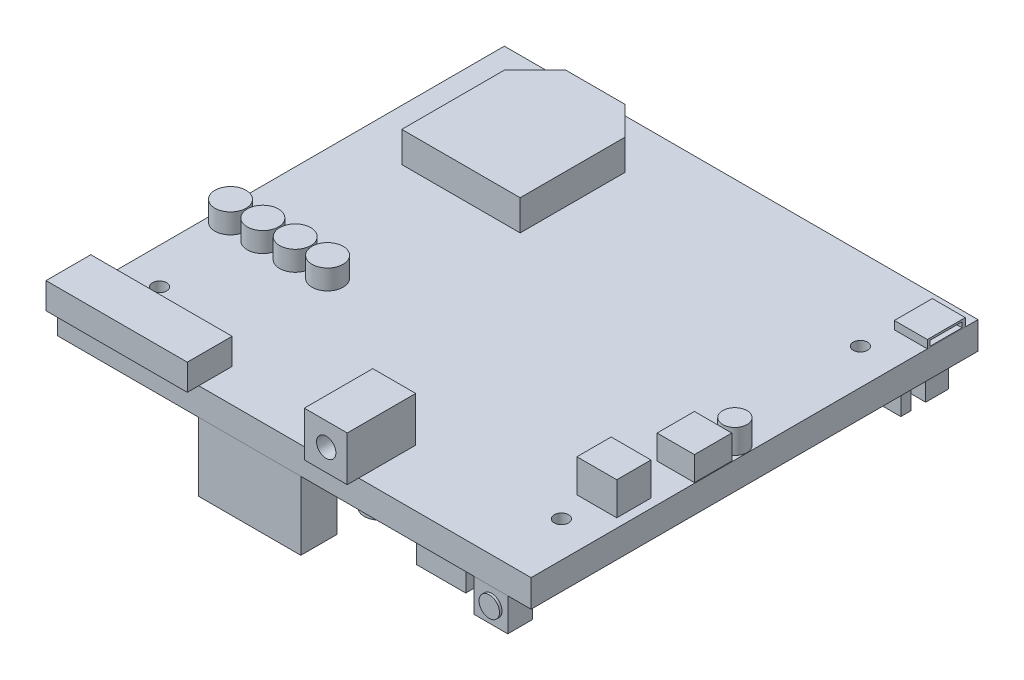
SolidWorks part; units mm, degrees
ref_plane "Front Plane" through (0, 0, 0) normal (0, 0, 1) x (1, 0, 0)
ref_plane "Top Plane" through (0, 0, 0) normal (0, 1, 0) x (1, 0, 0)
ref_plane "Right Plane" through (0, 0, 0) normal (1, 0, 0) x (0, 0, -1)
sketch "Sketch1" plane through (0, 0, 0) normal (0, 1, 0) x (1, 0, 0)
  line L1 (-85.1717, 91.186) -> (11.4753, 91.186)
  line L2 (-85.1717, 91.186) -> (-85.1717, 0)
  line L3 (-85.1717, 0) -> (11.4753, 0)
  line L4 (11.4753, 91.186) -> (11.4753, 0)
  dimension "D1" = 96.647
  dimension "D2" = 91.186
extrude "Boss-Extrude1" add sketch "Sketch1" along normal blind 5.588
sketch "Sketch2" plane through (0, 5.588, 0) normal (0, 1, 0) x (1, 0, 0)
  line L1 (11.4753, 91.186) -> (-85.1717, 91.186) construction
  line L2 (-85.1717, -2.3368) -> (-56.3427, -2.3368)
  line L3 (-85.1717, -2.3368) -> (-85.1717, 6.8072)
  line L4 (-85.1717, 6.8072) -> (-56.3427, 6.8072)
  line L5 (-56.3427, -2.3368) -> (-56.3427, 6.8072)
  line L6 (-32.4667, -2.3368) -> (-23.7037, -2.3368)
  line L7 (-32.4667, -2.3368) -> (-32.4667, 11.6332)
  line L8 (-32.4667, 11.6332) -> (-23.7037, 11.6332)
  line L9 (-23.7037, -2.3368) -> (-23.7037, 11.6332)
  line L10 (-74.7069, 80.8482) -> (-68.5601, 86.995)
  line L11 (-68.5601, 86.995) -> (-56.3427, 86.995)
  line L12 (-74.7069, 80.8482) -> (-74.7069, 59.7916)
  line L13 (-74.7069, 59.7916) -> (-50.5515, 59.7916)
  line L14 (-85.1717, 91.186) -> (-85.1717, 0) construction
  line L15 (-85.1717, 0) -> (11.4753, 0) construction
  line L16 (11.4753, 0) -> (11.4753, 91.186) construction
  line L17 (1.5185, 26.289) -> (9.6465, 26.289)
  line L18 (1.5185, 26.289) -> (1.5185, 19.304)
  line L19 (1.5185, 19.304) -> (9.6465, 19.304)
  line L20 (9.6465, 26.289) -> (9.6465, 19.304)
  line L21 (3.7283, 41.0718) -> (11.3483, 41.0718)
  line L22 (3.7283, 41.0718) -> (3.7283, 33.4518)
  line L23 (3.7283, 33.4518) -> (11.3483, 33.4518)
  line L24 (11.3483, 41.0718) -> (11.3483, 33.4518)
  line L25 (11.4753, 88.5952) -> (4.7443, 88.5952)
  line L26 (11.4753, 88.5952) -> (11.4753, 80.8482)
  line L27 (11.4753, 80.8482) -> (4.7443, 80.8482)
  line L28 (4.7443, 88.5952) -> (4.7443, 80.8482)
  line L29 (-50.5515, 81.2038) -> (-50.5515, 59.7916)
  line L30 (-68.5601, 86.995) -> (-56.3427, 86.995)
  line L31 (-56.3427, 86.995) -> (-50.5515, 81.2038)
  circle A0 centre (-81.9967, 32.131) radius 3.175
  circle A1 centre (-75.3927, 32.131) radius 3.175
  circle A2 centre (-68.7887, 32.131) radius 3.175
  circle A3 centre (-62.1847, 32.131) radius 3.175
  circle A4 centre (8.9353, 44.1198) radius 2.4765
  line M5 (-85.1717, 91.186) -> (-85.1717, 0)
  line M6 (-85.1717, 0) -> (11.4753, 0)
  line M7 (11.4753, 0) -> (11.4753, 91.186)
  dimension "D1" = 6.35
  dimension "D14" = 4.953
  dimension "D22" = 2.54
  dimension "D2" = 59.055
  dimension "D4" = 2.3368
  dimension "D5" = 2.3368
  dimension "D6" = 23.876
  dimension "D7" = 28.829
  dimension "D8" = 9.144
  dimension "D9" = 8.763
  dimension "D10" = 13.97
  dimension "D11" = 19.304
  dimension "D12" = 1.8288
  dimension "D13" = 0.127
  dimension "D15" = 2.5908
  dimension "D16" = 4.191
  dimension "D17" = 10.4648
  dimension "D18" = 8.128
  dimension "D19" = 6.985
  dimension "D20" = 7.1628
  dimension "D21" = 3.048
  dimension "D23" = 7.747
  dimension "D24" = 6.731
  dimension "D25" = 7.62
  dimension "D26" = 24.1554
  dimension "D27" = 7.62
  dimension "D3" = 4
extrude "Boss-Extrude2" add sketch "Sketch2" along normal blind 6.223 contours L31 L11 L10 L12 L13 L29 region at (-62.5981, 5.588, -72.7272)
extrude "Boss-Extrude3" add sketch "Sketch2<3>" along normal blind 4.064 separate body contours A0 | A1 | A2 | A3 region at (-81.9967, 5.588, -32.131) region at (-75.3927, 5.588, -32.131) region at (-68.7887, 5.588, -32.131) region at (-62.1847, 5.588, -32.131)
sketch "Sketch2<3>" plane through (0, 5.588, 0) normal (0, 1, 0) x (1, 0, 0) same geometry as "Sketch2"
extrude "Boss-Extrude4" add sketch "Sketch2<4>" along normal blind 5.334 separate body contours L5 L4 M6 M5 | L2 L5 L3 M6 region at (-70.7572, 5.588, 1.1684) region at (-70.7572, 5.588, -3.4036)
sketch "Sketch2<4>" plane through (0, 5.588, 0) normal (0, 1, 0) x (1, 0, 0) same geometry as "Sketch2"
extrude "Boss-Extrude5" add sketch "Sketch2<5>" along normal blind 9.144 separate body contours L9 L8 L7 M6 | L6 L9 L7 M6 region at (-28.0852, 5.588, -5.8166) region at (-28.0852, 5.588, 1.1684)
sketch "Sketch2<5>" plane through (0, 5.588, 0) normal (0, 1, 0) x (1, 0, 0) same geometry as "Sketch2"
extrude "Boss-Extrude6" add sketch "Sketch2<6>" along normal blind 6.731 separate body contours L20 L17 L18 L19 region at (5.5825, 5.588, -22.7965)
sketch "Sketch2<6>" plane through (0, 5.588, 0) normal (0, 1, 0) x (1, 0, 0) same geometry as "Sketch2"
extrude "Boss-Extrude7" add sketch "Sketch2<7>" along normal blind 4.953 separate body contours L24 L21 L22 L23 | A4 region at (7.5383, 5.588, -37.2618) region at (8.9353, 5.588, -44.1198)
sketch "Sketch2<7>" plane through (0, 5.588, 0) normal (0, 1, 0) x (1, 0, 0) same geometry as "Sketch2"
extrude "Boss-Extrude8" add sketch "Sketch2<8>" along normal blind 1.651 separate body contours L25 L28 L27 M7 region at (8.1098, 5.588, -84.7217)
sketch "Sketch2<8>" plane through (0, 5.588, 0) normal (0, 1, 0) x (1, 0, 0) same geometry as "Sketch2"
sketch "Sketch3" plane through (0, 0, 0) normal (0, -1, 0) x (1, 0, 0)
  line L0 (11.4753, -91.186) -> (-85.1717, -91.186) construction
  line L1 (-81.4887, -79.121) -> (-61.1687, -79.121)
  line L2 (-81.4887, -79.121) -> (-81.4887, -81.153)
  line L3 (-81.4887, -81.153) -> (-61.1687, -81.153)
  line L4 (-61.1687, -79.121) -> (-61.1687, -81.153)
  line L5 (-81.4887, -84.201) -> (-61.1687, -84.201)
  line L6 (-81.4887, -84.201) -> (-81.4887, -88.9)
  line L7 (-81.4887, -88.9) -> (-61.1687, -88.9)
  line L8 (-61.1687, -84.201) -> (-61.1687, -88.9)
  line L9 (-85.1717, -91.186) -> (-85.1717, 0) construction
  line L10 (-58.5017, -79.121) -> (-38.1817, -79.121)
  line L11 (-58.5017, -79.121) -> (-58.5017, -81.153)
  line L12 (-58.5017, -81.153) -> (-38.1817, -81.153)
  line L13 (-38.1817, -79.121) -> (-38.1817, -81.153)
  line L14 (-58.5017, -84.201) -> (-38.1817, -84.201)
  line L15 (-58.5017, -84.201) -> (-58.5017, -88.9)
  line L16 (-58.5017, -88.9) -> (-38.1817, -88.9)
  line L17 (-38.1817, -84.201) -> (-38.1817, -88.9)
  line L18 (-35.5147, -79.121) -> (-15.1947, -79.121)
  line L19 (-35.5147, -79.121) -> (-35.5147, -81.153)
  line L20 (-35.5147, -81.153) -> (-15.1947, -81.153)
  line L21 (-15.1947, -79.121) -> (-15.1947, -81.153)
  line L22 (-35.5147, -84.201) -> (-15.1947, -84.201)
  line L23 (-35.5147, -84.201) -> (-35.5147, -88.9)
  line L24 (-35.5147, -88.9) -> (-15.1947, -88.9)
  line L25 (-15.1947, -84.201) -> (-15.1947, -88.9)
  line L26 (-12.5277, -79.121) -> (7.7923, -79.121)
  line L27 (-12.5277, -79.121) -> (-12.5277, -81.153)
  line L28 (-12.5277, -81.153) -> (7.7923, -81.153)
  line L29 (7.7923, -79.121) -> (7.7923, -81.153)
  line L30 (-12.5277, -84.201) -> (7.7923, -84.201)
  line L31 (-12.5277, -84.201) -> (-12.5277, -88.9)
  line L32 (-12.5277, -88.9) -> (7.7923, -88.9)
  line L33 (7.7923, -84.201) -> (7.7923, -88.9)
  line L34 (11.4753, 0) -> (11.4753, -91.186) construction
  dimension "D1" = 2.286
  dimension "D2" = 3.048
  dimension "D3" = 4.699
  dimension "D4" = 2.032
  dimension "D5" = 3.683
  dimension "D6" = 3.683
  dimension "D7" = 20.32
  dimension "D8" = 20.32
  dimension "D10" = 3.683
  dimension "D11" = 2.667
  dimension "D12" = 2.667
  dimension "D9" = 2.667
  dimension "D13" = 20.32
  dimension "D14" = 4.699
  dimension "D15" = 2.032
extrude "Boss-Extrude9" add sketch "Sketch3" along normal blind 7.366 separate body
sketch "Sketch4" plane through (0, 0, 0) normal (0, -1, 0) x (1, 0, 0)
  line L0 (-56.3427, 2.3368) -> (-56.3427, -6.8072) construction
  line L1 (-56.3427, 0) -> (-35.5147, 0)
  line L2 (-56.3427, 0) -> (-56.3427, -7.366)
  line L3 (-56.3427, -7.366) -> (-35.5147, -7.366)
  line L4 (-35.5147, 0) -> (-35.5147, -7.366)
  line L5 (-85.1717, 0) -> (11.4753, 0) construction
  dimension "D1" = 7.366
  dimension "D2" = 20.828
extrude "Boss-Extrude10" add sketch "Sketch4" along normal blind 13.97 separate body
sketch "Sketch5" plane through (0, 0, 0) normal (0, -1, 0) x (1, 0, 0)
  line L0 (-85.1717, -91.186) -> (-85.1717, 0) construction
  line L1 (-49.2307, -46.99) -> (-24.2117, -46.99)
  line L2 (-49.2307, -46.99) -> (-49.2307, -50.927)
  line L3 (-49.2307, -50.927) -> (-24.2117, -50.927)
  line L4 (-24.2117, -46.99) -> (-24.2117, -50.927)
  line L5 (-85.1717, 0) -> (11.4753, 0) construction
  dimension "D1" = 25.019
  dimension "D2" = 3.937
  dimension "D3" = 35.941
  dimension "D4" = 46.99
extrude "Boss-Extrude11" add sketch "Sketch5" along normal blind 2.032 separate body
sketch "Sketch6" plane through (0, 0, 0) normal (0, -1, 0) x (1, 0, 0)
  line L0 (-85.1717, 0) -> (11.4753, 0) construction
  line L1 (-85.1717, -91.186) -> (-85.1717, 0) construction
  circle A0 centre (-28.2757, -8.763) radius 3.048
  dimension "D1" = 6.096
  dimension "D2" = 8.763
  dimension "D3" = 56.896
extrude "Boss-Extrude12" add sketch "Sketch6" along normal blind 6.35 separate body
sketch "Sketch7" plane through (0, 0, 0) normal (0, -1, 0) x (1, 0, 0)
  line L1 (-23.0687, -7.112) -> (-18.3697, -7.112)
  line L2 (-23.0687, -7.112) -> (-23.0687, -11.811)
  line L3 (-23.0687, -11.811) -> (-18.3697, -11.811)
  line L4 (-18.3697, -7.112) -> (-18.3697, -11.811)
  line L5 (11.4753, 0) -> (11.4753, -91.186) construction
  line L6 (-1029.7997, -11.811) -> (48970.2003, -11.811) construction
  dimension "D1" = 4.699
  dimension "D3" = 29.845
extrude "Boss-Extrude13" add sketch "Sketch7" along normal blind 1.651 separate body
sketch "Sketch8" plane through (0, 0, 0) normal (0, -1, 0) x (1, 0, 0)
  line L0 (-85.1717, 0) -> (11.4753, 0) construction
  line L1 (-13.1627, -1.27) -> (-3.1297, -1.27)
  line L2 (-13.1627, -1.27) -> (-13.1627, -11.303)
  line L3 (-13.1627, -11.303) -> (-3.1297, -11.303)
  line L4 (-3.1297, -1.27) -> (-3.1297, -11.303)
  line L5 (11.4753, 0) -> (11.4753, -91.186) construction
  dimension "D1" = 1.27
  dimension "D2" = 14.605
  dimension "D3" = 10.033
  dimension "D4" = 10.033
extrude "Boss-Extrude14" add sketch "Sketch8" along normal blind 5.08 separate body
sketch "Sketch10" plane through (0, 0, 0) normal (0, -1, 0) x (1, 0, 0)
  line L0 (-85.1717, 0) -> (11.4753, 0) construction
  line L1 (-0.1452, 0) -> (6.7128, 0)
  line L2 (-0.1452, 0) -> (-0.1452, -5.08)
  line L3 (-0.1452, -5.08) -> (6.7128, -5.08)
  line L4 (6.7128, 0) -> (6.7128, -5.08)
  line L5 (11.4753, 0) -> (11.4753, -91.186) construction
  dimension "D1" = 6.858
  dimension "D2" = 5.08
  dimension "D3" = 4.7625
extrude "Boss-Extrude15" add sketch "Sketch10" along normal blind 6.731 separate body
sketch "Sketch11" plane through (0, 0, 0) normal (0, -1, 0) x (1, 0, 0)
  line L0 (-995.8272, -12.0142) -> (49004.1728, -12.0142) construction
  line L1 (-995.8272, -75.946) -> (49004.1728, -75.946) construction
  line L2 (-79.2789, -1074.4855) -> (-79.2789, 48925.5145) construction
  line L3 (5.6333, -1074.9935) -> (5.6333, 48925.0065) construction
  line L5 (11.4753, 0) -> (11.4753, -91.186) construction
  line L7 (11.4753, -91.186) -> (-85.1717, -91.186) construction
  circle A0 centre (-77.8184, -13.4747) radius 1.4605
  circle A1 centre (-77.8184, -74.4855) radius 1.4605
  circle A2 centre (4.1728, -74.4855) radius 1.4605
  circle A3 centre (4.1728, -13.4747) radius 1.4605
  dimension "D1" = 5.842
  dimension "D2" = 15.24
  dimension "D3" = 2.921
  dimension "D4" = 2.921
  dimension "D5" = 2.921
  dimension "D6" = 2.921
  dimension "D7" = 61.0108
  dimension "D8" = 81.9912
extrude "Cut-Extrude1" cut sketch "Sketch11" against normal through all
sketch "Sketch12" plane through (0, 0, 0) normal (0, 0, 1) x (1, 0, 0)
  circle A0 centre (3.4438, -3.2951) radius 2.0863
sketch "Sketch13" plane through (11.4753, 0, 0) normal (1, 0, 0) x (0, 0, -1)
  line L1 (87.9374, 5.7729) -> (81.4346, 5.7729)
  line L2 (87.9374, 5.7729) -> (87.9374, 6.8252)
  line L3 (87.9374, 6.8252) -> (81.4346, 6.8252)
  line L4 (81.4346, 5.7729) -> (81.4346, 6.8252)
extrude "Cut-Extrude3" cut sketch "Sketch13" against normal blind 2.54
extrude "Boss-Extrude16" add sketch "Sketch12" along normal blind 0.508
sketch "Sketch14" plane through (0, 0, 2.3368) normal (0, 0, 1) x (1, 0, 0)
  circle A0 centre (-27.9958, 10.0545) radius 1.9737
extrude "Cut-Extrude4" cut sketch "Sketch14" against normal blind 4.064
